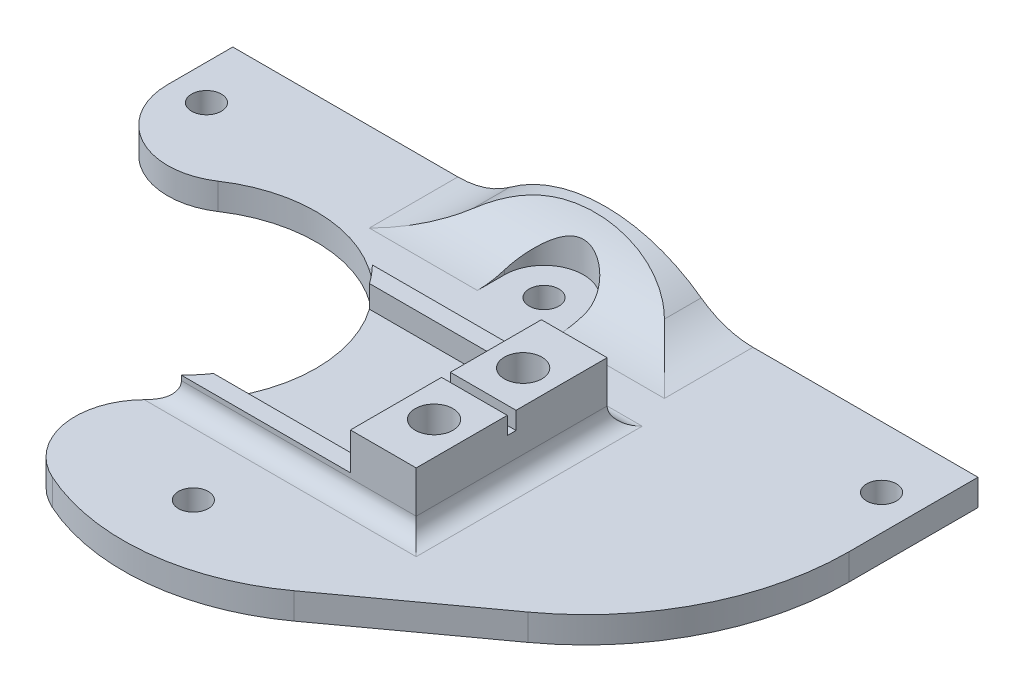
SolidWorks part; units mm, degrees
ref_plane "Plan de face" through (0, 0, 0) normal (0, 0, 1) x (1, 0, 0)
ref_plane "Plan de dessus" through (0, 0, 0) normal (0, 1, 0) x (1, 0, 0)
ref_plane "Plan de droite" through (0, 0, 0) normal (1, 0, 0) x (0, 0, -1)
sketch "Esquisse2" plane through (0, 0, 0) normal (0, 1, 0) x (1, 0, 0)
  line L0 (-42.5, 0) -> (42.5, 0)
  line L1 (42.5, 0) -> (42.5, -30)
  line L2 (42.5, -30) -> (14.7059, -50.2172)
  line L3 (-14.7059, -50.2172) -> (-42.5, -30)
  line L4 (-42.5, -30) -> (-42.5, 0)
  line L5 (-42.5, -30) -> (42.5, -30) construction
  arc A0 (14.7059, -50.2172) -> (-14.7059, -50.2172) centre (0, -30) cw
  point P7 (0, 0)
  point P10 (0, -55)
  dimension "D1" = 30
  dimension "D2" = 85
  dimension "D3" = 30
  dimension "25" = 25
extrude "Boss.-Extru.1" add sketch "Esquisse2" along normal blind 3
fillet "Congé1" radius 30 2 edges at (42.5, 1.5, 30) (-42.5, 1.5, 30)
sketch "Esquisse3" plane through (42.5, 0, 0) normal (1, 0, 0) x (0, 0, -1)
  line L1 (0, 0) -> (-2, 0)
  line L2 (0, 0) -> (0, 2)
  line L3 (0, 2) -> (-2, 2)
  line L4 (-2, 0) -> (-2, 2)
  dimension "D1" = 2
  dimension "D2" = 2
extrude "Enlèv. mat.-Extru.1" cut sketch "Esquisse3" against normal through all
hole_wizard "Dégagement M32" positions "Esquisse4" profile "Esquisse5" size "M3" standard "Ansi Metric" slot yes end condition through all
sketch "Esquisse4" plane through (0, 3, 0) normal (0, 1, 0) x (1, 0, 0)
  line L0 (-42.5, 0) -> (-42.5, -14.7247) construction
  line L1 (42.5, -14.7247) -> (42.5, 0) construction
  line L2 (42.5, 0) -> (-42.5, 0) construction
  point P0 (-38.5, -7)
  point P2 (0, -7)
  point P4 (38.5, -7)
  point P6 (0, -47)
  dimension "D1" = 4
  dimension "D2" = 4
  dimension "D3" = 7
  dimension "D4" = 40
sketch "Esquisse5" plane through (-38.5, 3, 7) normal (1, 0, 0) x (0, 0, 1)
  line L0 (0, 0) -> (0, 3)
  line L1 (0, 3) -> (1.7, 3)
  line L2 (1.7, 3) -> (1.7, 0)
  line L5 (1.7, 0) -> (0, 0)
  line L11 (0, -6.35) -> (0, 107.95) construction
  dimension "Diamètre du perçage jusqu'au prochain" = 3.4
  dimension "Profondeur du perçage jusqu'au prochain" = 3
sketch "Esquisse6" plane through (0, 3, 0) normal (0, 1, 0) x (1, 0, 0)
  line L0 (42.5, 0) -> (-42.5, 0) construction
  circle A0 centre (-21.5, -27) radius 15.5
  dimension "D2" = 31
  dimension "D1" = 21.5
  dimension "25" = 27
extrude "Enlèv. mat.-Extru.2" cut sketch "Esquisse6" against normal blind 3
fillet "Congé2" radius 8 2 edges at (-35.0731, 1.5, 34.4846) (-26.4151, 1.5, 41.7001)
sketch "Esquisse7" plane through (0, 0, 0) normal (0, -1, 0) x (1, 0, 0)
  line L0 (-42.5, 0) -> (42.5, 0) construction
  line L1 (42.5, 14.7247) -> (42.5, 2) construction
  circle A0 centre (21.5, 27) radius 2.55
  dimension "D1" = 5.1
  dimension "D2" = 27
  dimension "D3" = 21
extrude "Enlèv. mat.-Extru.3" cut sketch "Esquisse7" against normal blind 1
sketch "Esquisse8" plane through (0, 3, 0) normal (0, 1, 0) x (1, 0, 0)
  line L0 (-8.8028, -18.11) -> (8.8097, -18.11)
  line L2 (8.8097, -35.89) -> (-8.8028, -35.89)
  line L3 (-10.4701, -16.11) -> (8.8097, -16.11)
  line L4 (8.8097, -16.11) -> (8.8097, -18.11)
  line L5 (8.8097, -37.89) -> (-10.4701, -37.89)
  line L9 (8.8097, -35.89) -> (8.8097, -37.89)
  line L10 (8.8097, -35.89) -> (8.8097, -18.11) construction
  arc A0 (-11.9355, -39.1971) -> (-30.0745, -14.0877) centre (-21.5, -27) ccw construction
  arc A1 (-10.4701, -37.89) -> (-8.8028, -35.89) centre (-21.5, -27) ccw
  arc A2 (-8.8028, -18.11) -> (-10.4701, -16.11) centre (-21.5, -27) ccw
  point P1 (8.8097, -27)
  point P5 (-21.5, -27)
  dimension "D1" = 17.78
  dimension "D3" = 2
  dimension "D4" = 2
  dimension "D5" = 17.6125
extrude "Boss.-Extru.2" add sketch "Esquisse8" along normal blind 2.54
sketch "Esquisse10" plane through (0, 3, 0) normal (0, 1, 0) x (1, 0, 0)
  line L0 (-10.4701, -37.89) -> (8.8097, -37.89) construction
  line L1 (8.8097, -16.11) -> (16.3097, -16.11)
  line L2 (8.8097, -16.11) -> (8.8097, -37.89)
  line L3 (8.8097, -37.89) -> (16.3097, -37.89)
  line L4 (16.3097, -16.11) -> (16.3097, -37.89)
  dimension "D1" = 7.5
extrude "Boss.-Extru.4" add sketch "Esquisse10" along normal blind 6.77
hole_wizard "Dégagement M42" positions "Esquisse11" profile "Esquisse12" size "M4" standard "Ansi Metric" slot yes end condition through all
sketch "Esquisse11" plane through (0, 9.77, 0) normal (0, 1, 0) x (1, 0, 0)
  line L0 (16.3097, -16.11) -> (8.8097, -16.11) construction
  line L1 (16.3097, -37.89) -> (16.3097, -16.11) construction
  point P0 (12.5397, -21.92)
  point P2 (12.5397, -32.08)
  dimension "D1" = 5.81
  dimension "D2" = 10.16
  dimension "D3" = 3.77
sketch "Esquisse12" plane through (12.5397, 9.77, 21.92) normal (1, 0, 0) x (0, 0, 1)
  line L0 (0, 0) -> (0, 9.77)
  line L1 (0, 9.77) -> (2.15, 9.77)
  line L2 (2.15, 9.77) -> (2.15, 0)
  line L5 (2.15, 0) -> (0, 0)
  line L11 (0, -6.35) -> (0, 107.95) construction
  dimension "Diamètre du perçage jusqu'au prochain" = 4.3
  dimension "Profondeur du perçage jusqu'au prochain" = 9.77
sketch "Esquisse15" plane through (0, 0, 0) normal (0, 0, -1) x (-1, 0, 0)
  line L0 (-16.3097, 3) -> (10.4701, 3) construction
  line L1 (-13.1624, 3) -> (13.1624, 3)
  line L2 (-42.5, 3) -> (42.5, 3) construction
  arc A0 (13.1624, 3) -> (-13.1624, 3) centre (0, -10) ccw
  dimension "D1" = 37
  dimension "D2" = 13
extrude "Boss.-Extru.5" add sketch "Esquisse15" against normal blind 0.1
fillet "Congé3" radius 10 1 edges at (0, 3, 0.1)
fillet "Congé4" radius 10 2 edges at (-13.1624, 3, 5.05) (13.1624, 3, 5.05)
sketch "Esquisse16" plane through (0, 3, 0) normal (0, 1, 0) x (1, 0, 0)
  line L0 (-4.5, -7) -> (-4.5, -13.5)
  line L1 (-4.5, -13.5) -> (4.5, -13.5)
  line L2 (4.5, -13.5) -> (4.5, -7)
  arc A0 (4.5, -7) -> (-4.5, -7) centre (0, -7) ccw
  dimension "4.5" = 4.5
  dimension "6.5" = 6.5
extrude "Enlèv. mat.-Extru.4" cut sketch "Esquisse16" along normal through all
sketch "Esquisse17" plane through (0, 0, 0) normal (0, -1, 0) x (1, 0, 0)
  circle A0 centre (21.5, 27) radius 2.55
  circle A1 centre (21.5, 27) radius 4
  dimension "D1" = 5.1
  dimension "D2" = 8
extrude "Boss.-Extru.6" add sketch "Esquisse17" along normal blind 5
fillet "Congé5" radius 2 3 edges at (2.9198, 3, 16.11) (2.9198, 3, 37.89) (16.3097, 3, 27)
sketch "Esquisse18" plane through (16.3097, 0, 0) normal (1, 0, 0) x (0, 0, -1)
  line L0 (-37.89, 9.77) -> (-16.11, 9.77) construction
  line L1 (-26.5, 9.77) -> (-27.5, 9.77)
  line L2 (-26.5, 9.77) -> (-26.5, 7.77)
  line L3 (-26.5, 7.77) -> (-27.5, 7.77)
  line L4 (-27.5, 9.77) -> (-27.5, 7.77)
  point P6 (-27, 9.77)
  point P7 (-27, 9.77)
  dimension "D1" = 2
  dimension "D2" = 1
extrude "Enlèv. mat.-Extru.5" cut sketch "Esquisse18" against normal up to surface (7.5 mm away) up to face at (8.8097, 5.9625, 27)
sketch "Esquisse19" plane through (42.5, 0, 0) normal (1, 0, 0) x (0, 0, -1)
  line L1 (-2, 2) -> (0, 2)
  line L2 (-2, 2) -> (-2, 0)
  line L3 (-2, 0) -> (0, 0)
  line L4 (0, 2) -> (0, 0)
extrude "Boss.-Extru.7" add sketch "Esquisse19" against normal up to surface (85 mm away) up to face at (-42.5, 1.6667, 3.1411)
